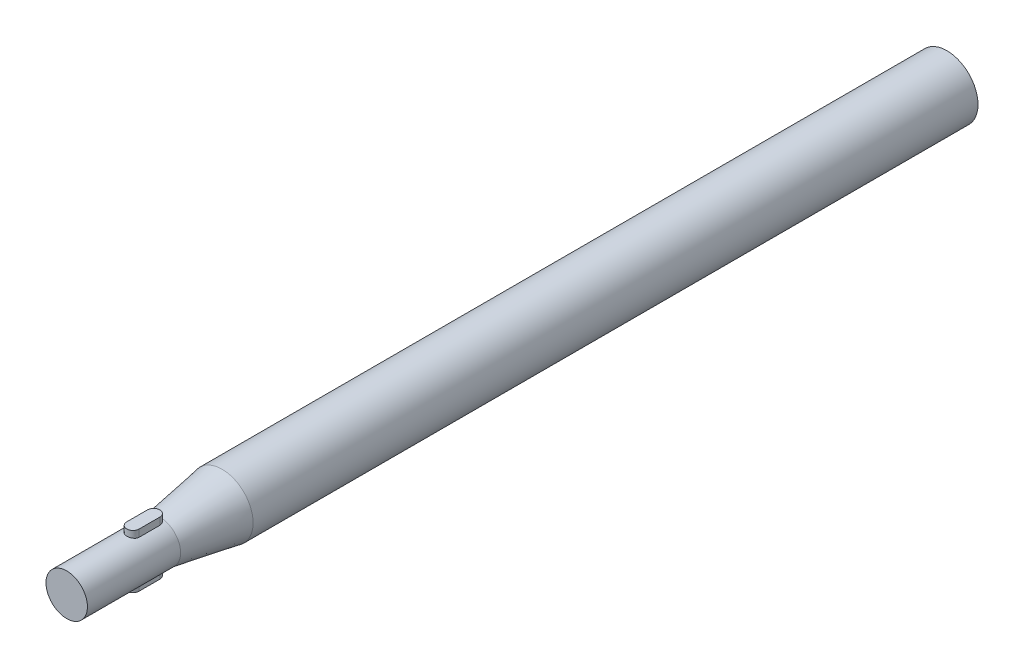
SolidWorks part; units mm, degrees
material "1.0503 (C45)"
ref_plane "Płaszczyzna przednia" through (0, 0, 0) normal (0, 0, 1) x (1, 0, 0)
ref_plane "Płaszczyzna górna" through (0, 0, 0) normal (0, 1, 0) x (1, 0, 0)
ref_plane "Płaszczyzna prawa" through (0, 0, 0) normal (1, 0, 0) x (0, 0, -1)
sketch "Szkic1" plane through (0, 0, 0) normal (0, 0, 1) x (1, 0, 0)
  circle A0 centre (0, 0) radius 15
  dimension "D1" = 30
extrude "Dodanie-wyciągnięcie1" add sketch "Szkic1" along normal blind 350
sketch "Szkic2" plane through (0, 0, 350) normal (0, 0, 1) x (1, 0, 0)
  circle A0 centre (0, 0) radius 10
  dimension "D1" = 20
extrude "Dodanie-wyciągnięcie2" add sketch "Szkic2" along normal blind 75
chamfer "Sfazowanie2" distance 5 distance2 30 1 edges at (10, 0, 350) first distance on face at (10, 0, 350)
ref_plane "Płaszczyzna1" through (0, 10, 0) normal (0, 1, 0) x (1, 0, 0)
sketch "Szkic3" plane through (0, 10, 0) normal (0, 1, 0) x (1, 0, 0)
  line L0 (0, -473.7322) -> (0, -517.9714) construction
  line L1 (10, -380) -> (-10, -380) construction
  line L3 (-3, -383) -> (-3, -393)
  line L5 (3, -383) -> (3, -393)
  arc A0 (-3, -393) -> (3, -393) centre (0, -393) ccw
  arc A1 (3, -383) -> (-3, -383) centre (0, -383) ccw
  dimension "D1" = 3
  dimension "D2" = 6
  dimension "D3" = 10
extrude "Dodanie-wyciągnięcie3" add sketch "Szkic3" against normal blind 3 and the other way blind 3
mirror "Lustro1" about plane through (0, 0, 0) normal (0, 1, 0) of "Dodanie-wyciągnięcie3"
